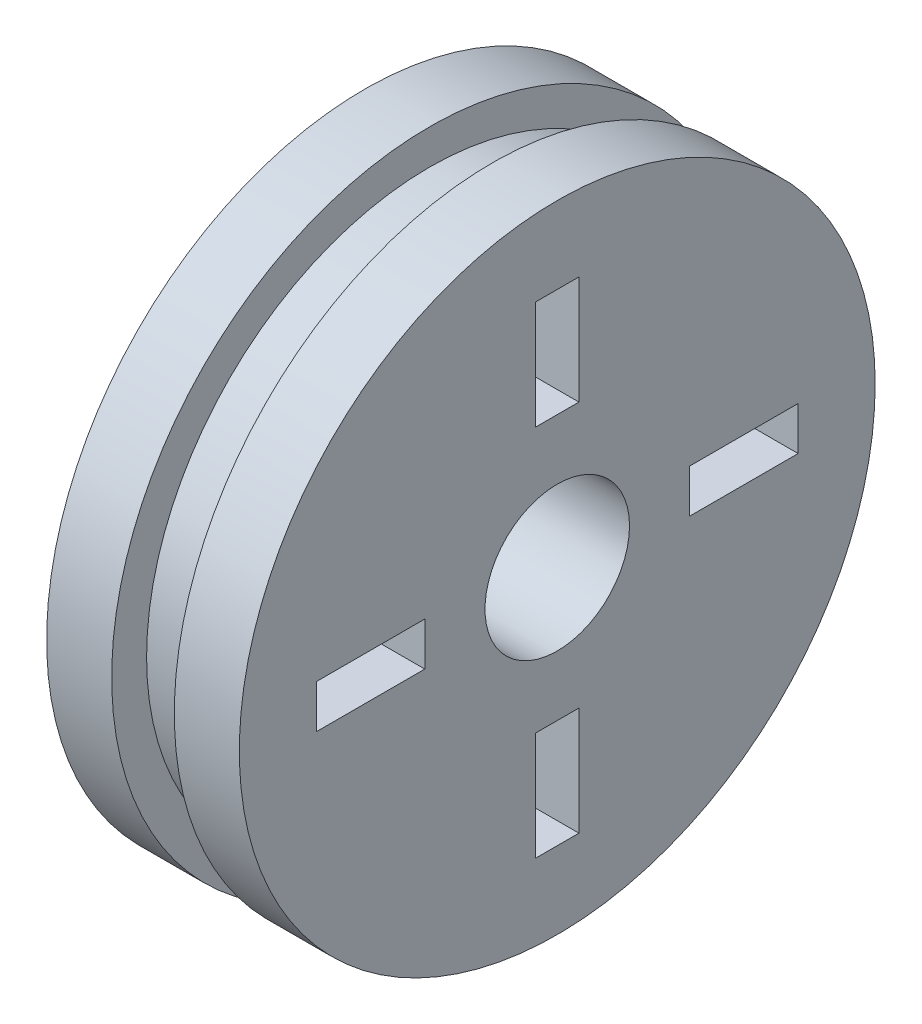
SolidWorks part; units mm, degrees
ref_plane "Front Plane" through (0, 0, 0) normal (0, 0, 1) x (1, 0, 0)
ref_plane "Top Plane" through (0, 0, 0) normal (0, 1, 0) x (1, 0, 0)
ref_plane "Right Plane" through (0, 0, 0) normal (1, 0, 0) x (0, 0, -1)
sketch "Sketch1" plane through (0, 0, 0) normal (1, 0, 0) x (0, 0, -1)
  circle A0 centre (-66, -65) radius 13.2
extrude "Boss-Extrude1" add sketch "Sketch1" along normal blind 8 from offset 77.2
sketch "Sketch2" plane through (0, 0, 0) normal (1, 0, 0) x (0, 0, -1)
  circle A0 centre (-66, -65) radius 20
extrude "Boss-Extrude2" add sketch "Sketch2" along normal blind 2.6 from offset 79.9 separate body
combine bodies "Combine1" operation type subtract main body 101 bodies to subtract 102
sketch "Sketch3" plane through (0, 0, 0) normal (1, 0, 0) x (0, 0, -1)
  circle A0 centre (-66, -65) radius 11.75
extrude "Boss-Extrude3" add sketch "Sketch3" along normal blind 2.6 from offset 79.9
sketch "Sketch4" plane through (0, 0, 0) normal (1, 0, 0) x (0, 0, -1)
  circle A0 centre (-66, -65) radius 4.6
extrude "Boss-Extrude4" add sketch "Sketch4" along normal blind 2.3 from offset 76.7 separate body
combine bodies "Combine2" operation type subtract main body 105 bodies to subtract 106
sketch "Sketch5" plane through (0, 0, 0) normal (0, 0, 1) x (1, 0, 0)
  line L1 (76.7, -65) -> (79, -65)
  line L2 (76.7, -65) -> (76.7, -53.5)
  line L3 (76.7, -53.5) -> (79, -53.5)
  line L4 (79, -65) -> (79, -53.5)
extrude "Boss-Extrude5" add sketch "Sketch5" along normal blind 6.6 from offset 62.7 separate body
combine bodies "Combine3" operation type subtract main body 107 bodies to subtract 108
sketch "Sketch6" plane through (0, 0, 0) normal (0, 0, 1) x (1, 0, 0)
  line L1 (76.2, -59.5) -> (86.2, -59.5)
  line L2 (76.2, -59.5) -> (76.2, -55)
  line L3 (76.2, -55) -> (86.2, -55)
  line L4 (86.2, -59.5) -> (86.2, -55)
extrude "Boss-Extrude6" add sketch "Sketch6" along normal blind 1.8 from offset 65.1 separate body
combine bodies "Combine4" operation type subtract main body 109 bodies to subtract 110
sketch "Sketch7" plane through (0, 0, 0) normal (0, 0, 1) x (1, 0, 0)
  line L1 (76.7, -76.5) -> (79, -76.5)
  line L2 (76.7, -76.5) -> (76.7, -65)
  line L3 (76.7, -65) -> (79, -65)
  line L4 (79, -76.5) -> (79, -65)
extrude "Boss-Extrude7" add sketch "Sketch7" along normal blind 6.6 from offset 62.7 separate body
combine bodies "Combine5" operation type subtract main body 111 bodies to subtract 112
sketch "Sketch8" plane through (0, 0, 0) normal (0, 0, 1) x (1, 0, 0)
  line L1 (76.2, -75) -> (86.2, -75)
  line L2 (76.2, -75) -> (76.2, -70.5)
  line L3 (76.2, -70.5) -> (86.2, -70.5)
  line L4 (86.2, -75) -> (86.2, -70.5)
extrude "Boss-Extrude8" add sketch "Sketch8" along normal blind 1.8 from offset 65.1 separate body
combine bodies "Combine6" operation type subtract main body 113 bodies to subtract 114
sketch "Sketch9" plane through (0, 0, 0) normal (0, 0, 1) x (1, 0, 0)
  line L1 (76.7, -68.3) -> (79, -68.3)
  line L2 (76.7, -68.3) -> (76.7, -61.7)
  line L3 (76.7, -61.7) -> (79, -61.7)
  line L4 (79, -68.3) -> (79, -61.7)
extrude "Boss-Extrude9" add sketch "Sketch9" along normal blind 11.5 from offset 66 separate body
combine bodies "Combine7" operation type subtract main body 115 bodies to subtract 116
sketch "Sketch10" plane through (0, 0, 0) normal (0, 0, 1) x (1, 0, 0)
  line L1 (76.2, -65.9) -> (86.2, -65.9)
  line L2 (76.2, -65.9) -> (76.2, -64.1)
  line L3 (76.2, -64.1) -> (86.2, -64.1)
  line L4 (86.2, -65.9) -> (86.2, -64.1)
extrude "Boss-Extrude10" add sketch "Sketch10" along normal blind 4.5 from offset 71.5 separate body
combine bodies "Combine8" operation type subtract main body 117 bodies to subtract 118
sketch "Sketch11" plane through (0, 0, 0) normal (0, 0, 1) x (1, 0, 0)
  line L1 (76.7, -68.3) -> (79, -68.3)
  line L2 (76.7, -68.3) -> (76.7, -61.7)
  line L3 (76.7, -61.7) -> (79, -61.7)
  line L4 (79, -68.3) -> (79, -61.7)
extrude "Boss-Extrude11" add sketch "Sketch11" along normal blind 11.5 from offset 54.5 separate body
combine bodies "Combine9" operation type subtract main body 119 bodies to subtract 120
sketch "Sketch12" plane through (0, 0, 0) normal (0, 0, 1) x (1, 0, 0)
  line L1 (76.2, -65.9) -> (86.2, -65.9)
  line L2 (76.2, -65.9) -> (76.2, -64.1)
  line L3 (76.2, -64.1) -> (86.2, -64.1)
  line L4 (86.2, -65.9) -> (86.2, -64.1)
extrude "Boss-Extrude12" add sketch "Sketch12" along normal blind 4.5 from offset 56 separate body
combine bodies "Combine10" operation type subtract main body 121 bodies to subtract 122
sketch "Sketch13" plane through (0, 0, 0) normal (1, 0, 0) x (0, 0, -1)
  circle A0 centre (-66, -65) radius 3
extrude "Boss-Extrude13" add sketch "Sketch13" along normal blind 10 from offset 76.2 separate body
combine bodies "Combine11" operation type subtract main body 123 bodies to subtract 124
